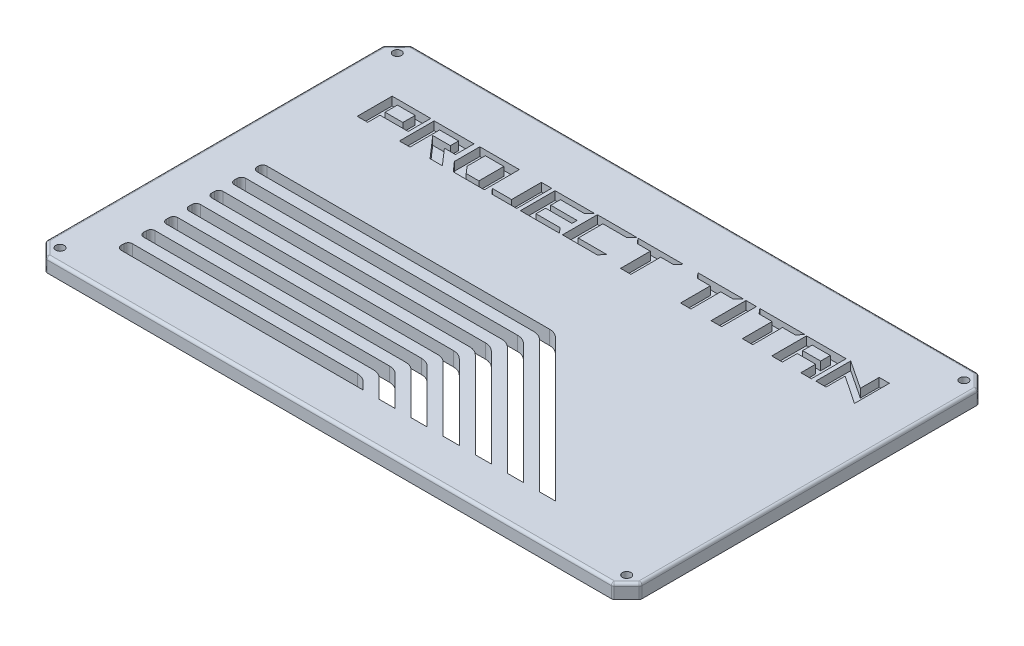
SolidWorks part; units mm, degrees
ref_plane "Front Plane" through (0, 0, 0) normal (0, 0, 1) x (1, 0, 0)
ref_plane "Top Plane" through (0, 0, 0) normal (0, 1, 0) x (1, 0, 0)
ref_plane "Right Plane" through (0, 0, 0) normal (1, 0, 0) x (0, 0, -1)
sketch "Sketch1" plane through (0, 0, 0) normal (0, 1, 0) x (1, 0, 0)
  line L1 (52.5, -34.5) -> (-52.5, -34.5)
  line L2 (52.5, -34.5) -> (52.5, 34.5)
  line L3 (52.5, 34.5) -> (-52.5, 34.5)
  line L4 (-52.5, -34.5) -> (-52.5, 34.5)
  line L5 (52.5, -34.5) -> (-52.5, 34.5) construction
  line L6 (52.5, 34.5) -> (-52.5, -34.5) construction
  point P0 (0, 0)
  dimension "D1" = 105
  dimension "D2" = 69
extrude "Boss-Extrude1" add sketch "Sketch1" along normal blind 5
extrude "Cut-Extrude1" cut sketch "Sketch2" against normal through all
sketch "Sketch2" plane through (17.0721, 0, 5.1034) normal (0, -1, 0) x (-1, 0, 0)
  line L0 (59.7281, 33.0909) -> (-27.1079, 33.0909)
  line L1 (-27.1079, 33.0909) -> (-27.1079, -24.4081)
  line L2 (-27.1079, -24.4081) -> (59.7281, -24.4081)
  line L3 (59.7281, -24.4081) -> (59.7281, 33.0909)
  line L8 (-26.1079, -23.4081) -> (58.7281, -23.4081) construction
  line L9 (-26.1079, 32.0909) -> (-26.1079, -23.4081) construction
  line L10 (58.7281, 32.0909) -> (-26.1079, 32.0909) construction
  line L11 (58.7281, -23.4081) -> (58.7281, 32.0909) construction
extrude "Cut-Extrude2" cut sketch "Sketch3" against normal blind 1
sketch "Sketch3" plane through (17.0721, 0, 5.1034) normal (0, -1, 0) x (-1, 0, 0)
  line L1 (59.8221, 30.7659) -> (54.5248, 30.7659)
  line L2 (59.8221, 30.7659) -> (59.8221, -16.2341) construction
  line L3 (59.8221, -16.2341) -> (54.5248, -16.2341)
  line L8 (65.3221, 30.2659) -> (60.3221, 30.2659) construction
  line L9 (60.3221, 30.2659) -> (60.3221, -15.7341) construction
  line L10 (60.3221, -15.7341) -> (65.3221, -15.7341) construction
  line L11 (65.3221, -15.7341) -> (65.3221, 30.2659) construction
  line L12 (54.5248, 30.7659) -> (54.5248, -16.2341)
  line L20 (65.8221, 30.7659) -> (59.8221, 30.7659)
  line L21 (59.8221, 30.7659) -> (59.8221, -16.2341) construction
  line L22 (59.8221, -16.2341) -> (65.8221, -16.2341)
  line L23 (65.8221, -16.2341) -> (65.8221, 30.7659)
extrude "Cut-Extrude3" cut sketch "Sketch4" against normal blind 1 contours L31 L28 L29 L17 L16 L19 | L19 L16 L17 | L30 L31 L19 L18 L17 L29 | L18 L19 L17 region at (15.76, 0, -28.9025) region at (12.8295, 0, -28.9025)
sketch "Sketch4" plane through (17.0721, 0, 5.1034) normal (0, -1, 0) x (-1, 0, 0)
  line L8 (69.5721, -29.3966) -> (69.5721, 69.6034)
  line L10 (-35.4279, 69.6034) -> (-35.4279, -29.3966)
  line L11 (-35.4279, -29.3966) -> (69.5721, -29.3966)
  line L16 (3.8121, 35.2559) -> (-1.1879, 35.2559)
  line L17 (-1.1879, 35.2559) -> (-1.1879, 32.7559)
  line L18 (-1.1879, 32.7559) -> (3.8121, 32.7559)
  line L19 (3.8121, 32.7559) -> (3.8121, 35.2559)
  line L20 (69.5721, 69.6034) -> (-35.4279, 69.6034)
  line L28 (4.3121, 35.7559) -> (-1.6879, 35.7559)
  line L29 (-1.6879, 35.7559) -> (-1.6879, 32.2559)
  line L30 (-1.6879, 32.2559) -> (4.3121, 32.2559)
  line L31 (4.3121, 32.2559) -> (4.3121, 35.7559)
extrude "Cut-Extrude4" cut sketch "Sketch5" against normal through all contours L3 L2 A3 L5 A2 L4 | L2 L3 L4 A4 L6 A5 region at (42.0883, 0, 0.4104)
sketch "Sketch5" plane through (17.0721, 0, 5.1034) normal (0, -1, 0) x (-1, 0, 0)
  line L2 (-27.1779, 33.1034) -> (-27.1779, 13.8376)
  line L3 (-27.1779, 5.1034) -> (-31.6779, 5.1034) construction
  line L4 (-31.6779, -0.8966) -> (-31.6779, 11.1034)
  line L5 (-30.1159, 12.6653) -> (-28.3501, 12.6653)
  line L6 (-29.4785, -3.0961) -> (-28.6478, -3.0961)
  line L7 (-27.1779, 5.1034) -> (-27.1779, 13.8376) construction
  line L8 (-27.1779, -4.566) -> (-18.8659, -4.566)
  line L9 (-27.1779, -4.566) -> (-27.1779, 5.1034)
  line L10 (-27.1779, 13.8376) -> (-18.8659, 13.8376)
  line L11 (-18.8659, -4.566) -> (-18.8659, 13.8376)
  line L12 (-27.1779, 13.8376) -> (-27.1779, 5.1034) construction
  line L13 (-27.1779, 5.1034) -> (-27.1779, -22.8966)
  arc A2 (-31.6779, 11.1034) -> (-30.1159, 12.6653) centre (-30.1159, 11.1034) cw
  arc A3 (-28.3501, 12.6653) -> (-27.1779, 13.8376) centre (-28.3501, 13.8376) ccw
  arc A4 (-31.6779, -0.8966) -> (-29.4785, -3.0961) centre (-29.4785, -0.8966) ccw
  arc A5 (-28.6478, -3.0961) -> (-27.1779, -4.566) centre (-28.6478, -4.566) cw
  point P8 (-31.6779, 5.1034)
extrude "Cut-Extrude7" cut sketch "Sketch9" against normal blind 4
sketch "Sketch9" plane through (17.0721, 0, 5.1034) normal (0, -1, 0) x (-1, 0, 0)
  circle A4 centre (-28.6779, -22.8966) radius 1.5 construction
  circle A5 centre (62.8221, -22.8966) radius 1.5 construction
  circle A6 centre (62.8221, 33.1034) radius 1.5 construction
  circle A7 centre (-28.6779, 33.1034) radius 1.5 construction
  circle A8 centre (-28.6779, 33.1034) radius 1
  circle A9 centre (62.8221, 33.1034) radius 1
  circle A10 centre (-28.6779, -22.8966) radius 1
  circle A11 centre (62.8221, -22.8966) radius 1
sketch "Sketch7" plane through (0, 5, 0) normal (0, 1, 0) x (1, 0, 0)
  line L1 (52.5, 34.5) -> (-52.5, 34.5)
  line L2 (52.5, 34.5) -> (52.5, 64.5)
  line L3 (52.5, 64.5) -> (-52.5, 64.5)
  line L4 (-52.5, 34.5) -> (-52.5, 64.5)
  line L5 (-52.5, -34.5) -> (52.5, -34.5)
  line L6 (-52.5, -34.5) -> (-52.5, -64.5)
  line L7 (-52.5, -64.5) -> (52.5, -64.5)
  line L8 (52.5, -34.5) -> (52.5, -64.5)
  line M17 (-52.5, -34.5) -> (52.5, -34.5)
  dimension "D1" = 30
  dimension "D2" = 30
extrude "Boss-Extrude2" add sketch "Sketch7" against normal up to surface (5 mm away) contours L8 L5 L7 M17 | L1 L4 L3 L2 region at (0, 5, 49.5) up to face at (-45.75, 0, -29)
sketch "Sketch8" plane through (0, 5, 0) normal (0, 1, 0) x (1, 0, 0)
  line L0 (52.5, 29.2726) -> (52.5, 64.5) construction
  line L1 (52.5, -64.5) -> (52.5, 64.5) construction
  line L2 (52.5, 46.8863) -> (26.68, 46.8863) construction
  line L3 (-52.5, 64.5) -> (-52.5, -64.5) construction
  line L4 (19.635, 46.8863) -> (19.635, 53.4863) construction
  line L5 (37.68, 40.2863) -> (26.68, 40.2863)
  line L6 (37.68, 40.2863) -> (37.68, 53.4863)
  line L7 (37.68, 53.4863) -> (26.68, 53.4863)
  line L8 (26.68, 40.2863) -> (26.68, 53.4863)
  line L9 (37.68, 40.2863) -> (26.68, 53.4863) construction
  line L10 (37.68, 53.4863) -> (26.68, 40.2863) construction
  line L11 (19.635, 40.2863) -> (8.635, 40.2863) construction
  line L12 (8.635, 40.2863) -> (8.635, 46.8863) construction
  line L13 (19.635, 53.4863) -> (8.635, 53.4863) construction
  line L14 (1.59, 46.8863) -> (1.59, 53.4863) construction
  line L15 (1.59, 40.2863) -> (-9.41, 40.2863) construction
  line L16 (-9.41, 46.8863) -> (-9.41, 53.4863) construction
  line L17 (1.59, 53.4863) -> (-9.41, 53.4863) construction
  line L18 (-16.455, 40.2863) -> (-16.455, 46.8863) construction
  line L19 (-16.455, 40.2863) -> (-27.455, 40.2863) construction
  line L20 (-27.455, 40.2863) -> (-27.455, 46.8863) construction
  line L21 (-16.455, 53.4863) -> (-27.455, 53.4863) construction
  line L22 (-34.5, 40.2863) -> (-34.5, 46.8863) construction
  line L23 (-34.5, 40.2863) -> (-45.5, 40.2863) construction
  line L24 (-45.5, 40.2863) -> (-45.5, 46.8863) construction
  line L25 (-34.5, 53.4863) -> (-45.5, 53.4863) construction
  line L26 (-45.5, 46.8863) -> (-45.5, 53.4863) construction
  line L27 (-34.5, 46.8863) -> (-34.5, 53.4863) construction
  line L28 (-27.455, 46.8863) -> (-34.5, 46.8863) construction
  line L29 (-34.5, 46.8863) -> (-52.5, 46.8863) construction
  line L30 (-16.455, 46.8863) -> (-27.455, 46.8863) construction
  line L31 (-27.455, 46.8863) -> (-27.455, 53.4863) construction
  line L32 (-16.455, 46.8863) -> (-16.455, 53.4863) construction
  line L33 (1.59, 40.2863) -> (1.59, 46.8863) construction
  line L34 (-9.41, 40.2863) -> (-9.41, 46.8863) construction
  line L35 (-9.41, 46.8863) -> (-16.455, 46.8863) construction
  line L36 (8.635, 46.8863) -> (8.635, 53.4863) construction
  line L37 (8.635, 46.8863) -> (1.59, 46.8863) construction
  line L38 (1.59, 46.8863) -> (-9.41, 46.8863) construction
  line L39 (19.635, 40.2863) -> (19.635, 46.8863) construction
  line L40 (26.68, 46.8863) -> (19.635, 46.8863) construction
  line L41 (19.635, 46.8863) -> (8.635, 46.8863) construction
  point P9 (32.18, 46.8863)
  point P14 (-40, 53.4863)
  dimension "D1" = 13.2
  dimension "D2" = 11
  dimension "D3" = 20.32
  dimension "D5" = 12.5
  dimension "D6" = 11
  dimension "D4" = 5
extrude "Cut-Extrude6" cut sketch "Sketch8" against normal through all
sketch "Sketch10" plane through (0, 5, 0) normal (0, 1, 0) x (1, 0, 0)
  line L0 (44.18, 27.9875) -> (44.18, 8.7342) construction
  line L1 (-52.5, 64.5) -> (52.5, 64.5)
  line L2 (-52.5, 64.5) -> (-52.5, -34.5)
  line L3 (-52.5, -34.5) -> (52.5, -34.5) construction
  line L4 (52.5, 64.5) -> (52.5, -34.5)
  line L5 (44.18, -9.6693) -> (44.18, -29.5115) construction
  line L6 (44.18, -29.5115) -> (-42.656, -29.5115) construction
  line L7 (-42.656, -29.5115) -> (-42.656, 27.9875) construction
  line L8 (-42.656, 27.9875) -> (44.18, 27.9875) construction
  line L9 (37.68, 40.2863) -> (37.68, 53.4863) construction
  line L10 (26.68, 40.2863) -> (37.68, 40.2863) construction
  line L11 (37.68, 53.4863) -> (26.68, 53.4863) construction
  line L12 (26.68, 53.4863) -> (26.68, 40.2863) construction
  line L29 (44.18, 27.9875) -> (44.18, 8.7342)
  line L30 (44.18, -9.6693) -> (44.18, -29.5115)
  line L31 (44.18, -29.5115) -> (-42.656, -29.5115)
  line L32 (-42.656, -29.5115) -> (-42.656, 27.9875)
  line L33 (-42.656, 27.9875) -> (44.18, 27.9875)
  line L34 (37.68, 40.2863) -> (37.68, 53.4863)
  line L35 (26.68, 40.2863) -> (37.68, 40.2863)
  line L36 (37.68, 53.4863) -> (26.68, 53.4863)
  line L37 (26.68, 53.4863) -> (26.68, 40.2863)
  line L54 (44.18, -9.6693) -> (44.18, 8.7342)
  line L59 (-52.5, 64.5) -> (-52.5, -64.5)
  line L60 (-52.5, -64.5) -> (52.5, -64.5)
  line L61 (52.5, -64.5) -> (52.5, 64.5)
  line L62 (52.5, 64.5) -> (-52.5, 64.5)
  line L63 (-52.5, 64.5) -> (-52.5, -64.5)
  line L64 (-52.5, -64.5) -> (52.5, -64.5)
  line L65 (52.5, -64.5) -> (52.5, 64.5)
  line L66 (52.5, 64.5) -> (-52.5, 64.5)
  line M11 (26.68, 40.2863) -> (26.68, 53.4863)
  line M12 (26.68, 53.4863) -> (37.68, 53.4863)
  line M13 (37.68, 53.4863) -> (37.68, 40.2863)
  line M14 (37.68, 40.2863) -> (26.68, 40.2863)
  line M31 (44.18, 27.9875) -> (44.18, 8.7342)
  line M32 (44.18, 8.7342) -> (44.25, 8.7342)
  arc M33 (44.25, 8.7342) -> (45.4223, 7.562) centre (45.4223, 8.7342) ccw
  line M34 (45.4223, 7.562) -> (47.188, 7.562)
  arc M35 (47.188, 7.562) -> (48.75, 6) centre (47.188, 6) cw
  line M36 (48.75, 6) -> (48.75, -6)
  arc M37 (48.75, -6) -> (46.5506, -8.1994) centre (46.5506, -6) cw
  line M38 (46.5506, -8.1994) -> (45.7199, -8.1994)
  arc M39 (45.7199, -8.1994) -> (44.25, -9.6693) centre (45.7199, -9.6693) ccw
  line M40 (44.25, -9.6693) -> (44.18, -9.6693)
  line M41 (44.18, -9.6693) -> (44.18, -29.5115)
  line M42 (44.18, -29.5115) -> (-42.656, -29.5115)
  line M43 (-42.656, -29.5115) -> (-42.656, 27.9875)
  line M44 (-42.656, 27.9875) -> (44.18, 27.9875)
  line M45 (-52.5, 64.5) -> (-52.5, -64.5)
  line M47 (52.5, -64.5) -> (52.5, 64.5)
  line M48 (52.5, 64.5) -> (-52.5, 64.5)
  line M70 (-52.5, -64.5) -> (52.5, -64.5)
  dimension "D1" = 0
extrude "Boss-Extrude3" add sketch "Sketch10" along normal blind 2 contours L3 M45 M47 M48 M44 M31 M32 M33 M34 M35 M36 M37 M38 M39 M40 M41 M42 M43 M14 M11 M12 M13 | L3 M45 M70 M47 | L54 M40 M39 M38 M37 M36 M35 M34 M33 M32 region at (-2.2738, 5, -29.4948) region at (0, 5, 49.5) region at (46.3986, 5, 0.2889)
sketch "Sketch11" plane through (0, 7, 0) normal (0, 1, 0) x (1, 0, 0)
  line L4 (-42.656, 27.9875) -> (-42.656, -29.5115)
  line L5 (44.18, 27.9875) -> (-42.656, 27.9875)
  line L6 (-42.656, -29.5115) -> (44.18, -29.5115)
  line L7 (44.18, -29.5115) -> (44.18, 27.9875)
  line L8 (36.68, -29.5115) -> (36.68, -27.5115) construction
  line L9 (44.18, -29.5115) -> (36.68, -29.5115)
  line L10 (44.18, -29.5115) -> (44.18, 27.9875)
  line L11 (44.18, 27.9875) -> (36.68, 27.9875)
  line L12 (36.68, -27.5115) -> (36.68, 25.9875)
  line L13 (-42.656, -29.5115) -> (36.68, -29.5115)
  line L14 (-42.656, -29.5115) -> (-42.656, -27.5115)
  line L15 (-40.656, -27.5115) -> (36.68, -27.5115)
  line L16 (36.68, -29.5115) -> (36.68, -27.5115) construction
  line L17 (-42.656, 27.9875) -> (36.68, 27.9875)
  line L18 (-42.656, 27.9875) -> (-42.656, 25.9875)
  line L19 (-40.656, 25.9875) -> (36.68, 25.9875)
  line L20 (36.68, 27.9875) -> (36.68, 25.9875) construction
  line L21 (-42.656, 27.9875) -> (-40.656, 27.9875)
  line L22 (-42.656, 27.9875) -> (-42.656, -29.5115)
  line L23 (-42.656, -29.5115) -> (-40.656, -29.5115)
  line L24 (-40.656, 25.9875) -> (-40.656, -27.5115)
  line L25 (-40.656, -27.5115) -> (-40.656, -29.5115) construction
  line L26 (-42.656, -27.5115) -> (-40.656, -27.5115) construction
  line L27 (-42.656, 25.9875) -> (-40.656, 25.9875) construction
  line L28 (-40.656, 27.9875) -> (-40.656, 25.9875) construction
  line L29 (36.68, 25.9875) -> (36.68, 27.9875) construction
  dimension "D1" = 7.5
  dimension "D2" = 2
  dimension "D3" = 2
  dimension "D4" = 2
extrude "Boss-Extrude4" add sketch "Sketch11" against normal blind 2 contours L13 L6 L5 L17 L4 L24 L19 L12 L15 region at (-41.656, 7, -26.946)
chamfer "Chamfer1" distance 1 angle 45 4 edges at (-1.988, 7, -25.9875) (-40.656, 7, 0.762) (-1.988, 7, 27.5115) (36.68, 7, 0.762)
sketch "Sketch12" plane through (0, 7, 0) normal (0, 1, 0) x (1, 0, 0)
  line L0 (-52.5, -64.5) -> (52.5, -64.5) construction
  line L1 (-52.5, -64.5) -> (-117.5, -64.5)
  line L2 (-52.5, -64.5) -> (-52.5, 64.5)
  line L3 (-52.5, 64.5) -> (-117.5, 64.5)
  line L4 (-117.5, -64.5) -> (-117.5, 64.5)
  line L5 (52.5, -64.5) -> (117.5, -64.5)
  line L6 (52.5, -64.5) -> (52.5, 64.5)
  line L7 (52.5, 64.5) -> (117.5, 64.5)
  line L8 (117.5, -64.5) -> (117.5, 64.5)
  line L9 (52.5, 64.5) -> (-52.5, 64.5) construction
  line L10 (-67.5, -28) -> (-102.5, -28) construction
  line L11 (-85, -45.5) -> (-85, -10.5) construction
  circle A0 centre (-85, -10.5) radius 6
  circle A1 centre (-85, -45.5) radius 6
  circle A2 centre (-102.5, -28) radius 6
  circle A3 centre (-67.5, -28) radius 6
  circle A4 centre (-85, -10.5) radius 8.5 construction
  circle A5 centre (-102.5, -28) radius 8.5 construction
  circle A6 centre (-67.5, -28) radius 8.5 construction
  circle A7 centre (-85, -45.5) radius 8.5 construction
  point P4 (-85, 64.5)
  point P19 (-85, -28)
  line M72 (-52.5, 64.5) -> (-52.5, -64.5)
  dimension "D3" = 12
  dimension "D7" = 17
  dimension "D8" = 17
  dimension "D1" = 65
  dimension "D2" = 65
  dimension "D4" = 35
  dimension "D5" = 75
  dimension "D6" = 35
extrude "Boss-Extrude5" add sketch "Sketch12" against normal up to surface (7 mm away) contours L4 L1 L3 M72 region at (-85, 7, -1.5968) up to face at (32.18, 0, -46.8863)
sketch "Sketch15" plane through (0, 7, 0) normal (0, 1, 0) x (1, 0, 0)
  line L0 (-117.5, -64.5) -> (52.5, -64.5) construction
  line L1 (-41.656, -28.5115) -> (37.68, -28.5115)
  line L2 (-41.656, -28.5115) -> (-41.656, -64.5)
  line L3 (-41.656, -64.5) -> (37.68, -64.5)
  line L4 (37.68, -28.5115) -> (37.68, -64.5)
  line L5 (-41.656, -46.5057) -> (37.68, -46.5057) construction
  circle A0 centre (-32.041, -46.5057) radius 3.1
  circle A1 centre (-12.041, -46.5057) radius 3.1
  circle A2 centre (7.959, -46.5057) radius 3.1
  circle A3 centre (27.959, -46.5057) radius 3.1
  dimension "D1" = 6.2
  dimension "D2" = 9.615
  dimension "D3" = 4
extrude "Cut-Extrude8" cut sketch "Sketch15" against normal through all contours A0 L5 | A1 L5 | L5 A1 | L5 A0 | A2 L5 | L5 A2 | A3 L5 | L5 A3 | A1 region at (-32.041, 7, 45.1901) region at (-32.041, 7, 47.8214) region at (27.959, 7, 47.8214) region at (27.959, 7, 45.1901) region at (-12.041, 7, 45.1901) region at (-12.041, 7, 47.8214) region at (7.959, 7, 47.8214) region at (7.959, 7, 45.1901)
sketch "Sketch16" plane through (0, 0, 0) normal (0, -1, 0) x (1, 0, 0)
  circle A0 centre (27.959, 46.5057) radius 3.1 construction
  circle A1 centre (7.959, 46.5057) radius 3.1 construction
  circle A2 centre (-12.041, 46.5057) radius 3.1 construction
  circle A3 centre (-32.041, 46.5057) radius 3.1 construction
  circle A4 centre (27.959, 46.5057) radius 3.1
  circle A5 centre (7.959, 46.5057) radius 3.1
  circle A6 centre (-12.041, 46.5057) radius 3.1
  circle A7 centre (-32.041, 46.5057) radius 3.1
  circle A8 centre (-32.041, 46.5057) radius 5.5
  circle A9 centre (-12.041, 46.5057) radius 5.5
  circle A10 centre (7.959, 46.5057) radius 5.5
  circle A11 centre (27.959, 46.5057) radius 5.5
  dimension "D1" = 11
extrude "Cut-Extrude9" cut sketch "Sketch16" against normal blind 3
sketch "Sketch18" plane through (0, 0, 0) normal (0, -1, 0) x (1, 0, 0)
  circle A0 centre (-85, 45.5) radius 10
  circle A1 centre (-102.5, 28) radius 10
  circle A2 centre (-85, 10.5) radius 10
  circle A3 centre (-67.5, 28) radius 10
  dimension "D1" = 20
extrude "Cut-Extrude10" cut sketch "Sketch18" against normal blind 3
chamfer "Chamfer2" distance 1 angle 45 4 edges at (-85, 0, 0.5) (-67.5, 0, 18) (-102.5, 0, 18) (-85, 0, 35.5)
sketch "Sketch19" plane through (0, 0, 0) normal (0, -1, 0) x (1, 0, 0)
  line L0 (-117.5, -64.5) -> (52.5, -64.5) construction
  line L1 (-42.656, -27.9875) -> (26.68, -27.9875)
  line L2 (-42.656, -27.9875) -> (-42.656, -64.5)
  line L4 (26.68, -27.9875) -> (26.68, -64.5)
  line L5 (26.68, -64.5) -> (-7.988, -64.5) construction
  line L6 (26.68, -64.5) -> (-7.988, -64.5) construction
  line L7 (18.196, -64.5) -> (0.496, -64.5)
  line L8 (18.196, -64.5) -> (18.196, -51)
  line L9 (18.196, -51) -> (0.496, -51)
  line L10 (0.496, -64.5) -> (0.496, -51)
  point P12 (9.346, -64.5)
  point P13 (9.346, -64.5)
  line M50 (-117.5, -64.5) -> (52.5, -64.5)
  dimension "D1" = 17.7
  dimension "D2" = 13.5
extrude "Cut-Extrude11" cut sketch "Sketch19" against normal blind 2 contours L10 L8 L9 M50 region at (9.346, 0, -57.75)
sketch "Sketch20" plane through (0, 2, 0) normal (0, -1, 0) x (1, 0, 0)
  line L0 (5.496, -62.5) -> (10.696, -62.5) construction
  line L1 (5.496, -61.0866) -> (10.696, -61.0866)
  line L3 (18.196, -64.5) -> (18.196, -51) construction
  line L4 (0.496, -64.5) -> (0.496, -51) construction
  line L5 (0.496, -64.5) -> (18.196, -64.5) construction
  line L6 (18.196, -64.5) -> (18.196, -51) construction
  line L7 (0.496, -64.5) -> (18.196, -64.5)
  line L8 (0.496, -64.5) -> (0.496, -61.0866)
  line L9 (0.496, -61.0866) -> (18.196, -61.0866)
  line L10 (18.196, -64.5) -> (18.196, -61.0866)
  line L12 (0.496, -51) -> (18.196, -51)
  line L13 (0.496, -51) -> (0.496, -55.2225)
  line L14 (0.496, -55.2225) -> (18.196, -55.2225)
  line L15 (18.196, -51) -> (18.196, -55.2225)
  point P2 (8.096, -62.5)
  line M2 (0.496, -51) -> (0.496, -64.5)
  line M4 (18.196, -64.5) -> (18.196, -51)
  line M5 (18.196, -51) -> (0.496, -51)
  dimension "D1" = 7.5
  dimension "D2" = 5
  dimension "D3" = 2
extrude "Cut-Extrude12" cut sketch "Sketch20" against normal blind 1 contours L10 L9 L1 | L14 M2 M4 M5 region at (9.346, 2, -62.7933) region at (9.346, 2, -53.1112)
sketch "Sketch22" plane through (0, 0, 0) normal (0, -1, 0) x (1, 0, 0)
  line L0 (-117.5, -64.5) -> (0.496, -64.5) construction
  line L1 (-24.8391, -64.5) -> (-60.3391, -64.5)
  line L2 (-24.8391, -64.5) -> (-24.8391, -54.5)
  line L3 (-24.8391, -54.5) -> (-60.3391, -54.5)
  line L4 (-60.3391, -64.5) -> (-60.3391, -54.5)
  circle A0 centre (-57.8391, -59.5) radius 1
  dimension "D4" = 2
  dimension "D1" = 10
  dimension "D2" = 35.5
  dimension "D3" = 2.5
extrude "Cut-Extrude13" cut sketch "Sketch22" against normal blind 2
sketch "Sketch23" plane through (0, 0, 0) normal (0, -1, 0) x (1, 0, 0)
  circle A1 centre (-57.8391, -59.5) radius 1
  circle A2 centre (-57.8391, -59.5) radius 1
  dimension "D1" = 0
extrude "Cut-Extrude14" cut sketch "Sketch23" against normal blind 4
sketch "Sketch24" plane through (0, 2, 0) normal (0, -1, 0) x (1, 0, 0)
  line L0 (-35.8391, -63) -> (-25.8391, -63) construction
  line L1 (-35.8391, -62.0036) -> (-25.8391, -62.0036)
  line L2 (-35.8391, -63.9964) -> (-25.8391, -63.9964)
  line L3 (-60.3391, -64.5) -> (-24.8391, -64.5) construction
  line L4 (-24.8391, -64.5) -> (-24.8391, -54.5) construction
  arc A0 (-35.8391, -62.0036) -> (-35.8391, -63.9964) centre (-35.8391, -63) ccw
  arc A1 (-25.8391, -63.9964) -> (-25.8391, -62.0036) centre (-25.8391, -63) ccw
  point P2 (-30.8391, -63)
  dimension "D1" = 1.5
  dimension "D2" = 6
  dimension "D3" = 10
extrude "Cut-Extrude15" cut sketch "Sketch24" against normal blind 1
sketch "Sketch25" plane through (0, 7, 0) normal (0, 1, 0) x (1, 0, 0)
  line L0 (52.5, 64.5) -> (-117.5, 64.5) construction
  line L1 (-117.5, -64.5) -> (-117.5, 64.5) construction
  circle A0 centre (-102.5, 44.5) radius 3.1
  circle A1 centre (-82.5, 44.5) radius 3.1
  dimension "D1" = 6.2
  dimension "D2" = 20
  dimension "D3" = 20
  dimension "D4" = 15
extrude "Cut-Extrude16" cut sketch "Sketch25" against normal through all
sketch "Sketch26" plane through (0, 0, 0) normal (0, -1, 0) x (1, 0, 0)
  circle A0 centre (-102.5, -44.5) radius 5.15
  circle A1 centre (-82.5, -44.5) radius 5.15
  dimension "D1" = 10.3
extrude "Cut-Extrude17" cut sketch "Sketch26" against normal blind 4
sketch "Sketch27" plane through (0, 7, 0) normal (0, 1, 0) x (1, 0, 0)
  line L1 (52.5, 64.5) -> (92.5, 64.5)
  line L2 (52.5, 64.5) -> (52.5, -64.5)
  line L3 (52.5, -64.5) -> (92.5, -64.5)
  line L4 (92.5, 64.5) -> (92.5, -64.5)
  dimension "D1" = 40
extrude "Boss-Extrude6" add sketch "Sketch27" against normal up to surface (7 mm away) up to face at (-102.5, 0, -49.65)
pattern_linear "LPattern1" count 2 spacing 40 along (1, 0, 0) of "Cut-Extrude17", "Cut-Extrude16"
sketch "Sketch28" plane through (0, 7, 0) normal (0, 1, 0) x (1, 0, 0)
  line L0 (37.68, -0.762) -> (92.5, 0) construction
  line L1 (37.68, 26.9875) -> (37.68, -28.5115) construction
  line L2 (92.5, -64.5) -> (92.5, 64.5) construction
  line L3 (37.68, -0.762) -> (65.09, -0.381)
  line L4 (92.5, 64.5) -> (-117.5, 64.5) construction
  line L6 (65.09, -0.381) -> (65.09, -64.5) construction
  line L7 (-117.5, -64.5) -> (92.5, -64.5) construction
  line L8 (72.5, 32.0595) -> (72.5, 64.5) construction
  circle A0 centre (62.5, 48.2798) radius 3.45
  circle A1 centre (62.5, 48.2798) radius 11.75 construction
  circle A2 centre (62.5, 16.2798) radius 3.45
  circle A3 centre (62.5, 16.2798) radius 11.75 construction
  circle A4 centre (62.5, -15.7202) radius 3.45
  circle A5 centre (62.5, -15.7202) radius 11.75 construction
  circle A6 centre (62.5, -47.7202) radius 3.45
  circle A7 centre (62.5, -47.7202) radius 11.75 construction
  point P17 (72.5, 48.2798)
  dimension "D2" = 6.9
  dimension "D3" = 30
  dimension "D1" = 4
extrude "Cut-Extrude18" cut sketch "Sketch28" against normal through all contours A0 | A2 | A4 | A6 region at (62.5, 7, -48.2798) region at (62.5, 7, -16.2798) region at (62.5, 7, 15.7202) region at (62.5, 7, 47.7202)
sketch "Sketch29" plane through (0, 7, 0) normal (0, 1, 0) x (1, 0, 0)
  line L0 (74.25, 48.2798) -> (92.5, 48.2798) construction
  line L1 (92.5, -64.5) -> (92.5, 64.5) construction
  circle A0 centre (62.5, 48.2798) radius 11.75 construction
  circle A1 centre (83.375, 48.2798) radius 3.45
  circle A2 centre (83.375, 16.2798) radius 3.45
  circle A3 centre (83.375, -15.7202) radius 3.45
  circle A4 centre (83.375, -47.7202) radius 3.45
  dimension "D1" = 6.9
  dimension "D2" = 4
extrude "Cut-Extrude19" cut sketch "Sketch29" against normal through all
sketch "Sketch30" plane through (0, 0, 0) normal (0, -1, 0) x (1, 0, 0)
  circle A0 centre (83.375, -48.2798) radius 5
  circle A1 centre (83.375, -16.2798) radius 5
  circle A2 centre (83.375, 15.7202) radius 5
  circle A3 centre (83.375, 47.7202) radius 5
  dimension "D1" = 10
  dimension "D2" = 4
extrude "Cut-Extrude20" cut sketch "Sketch30" against normal blind 4.5
sketch "Sketch31" plane through (0, 0, 0) normal (0, -1, 0) x (1, 0, 0)
  circle A0 centre (62.5, 47.7202) radius 5.5
  circle A1 centre (62.5, 15.7202) radius 5.5
  circle A2 centre (62.5, -16.2798) radius 5.5
  circle A3 centre (62.5, -48.2798) radius 5.5
  dimension "D1" = 11
  dimension "D2" = 4
extrude "Cut-Extrude21" cut sketch "Sketch31" against normal blind 2
sketch "Sketch32" plane through (0, 0, 0) normal (0, -1, 0) x (1, 0, 0)
  line L0 (69.9505, 49.2202) -> (70.9682, 49.2202)
  line L2 (61, 56.1884) -> (61, 55.1708)
  line L4 (64, 56.1884) -> (64, 55.1708)
  line L5 (54.0318, 49.2202) -> (55.0495, 49.2202)
  line L7 (54.0318, 46.2202) -> (55.0495, 46.2202)
  line L9 (69.9505, 46.2202) -> (70.9682, 46.2202)
  line L12 (64, 40.2697) -> (64, 39.2521)
  line L13 (61, 40.2697) -> (61, 39.2521)
  arc A0 (54.0318, 49.2202) -> (54.0318, 46.2202) centre (62.5, 47.7202) ccw
  arc A1 (55.0495, 49.2202) -> (55.0495, 46.2202) centre (62.5, 47.7202) ccw
  circle A2 centre (62.5, 47.7202) radius 8.6 construction
  circle A3 centre (62.5, 47.7202) radius 7.6 construction
  arc A4 (64, 56.1884) -> (61, 56.1884) centre (62.5, 47.7202) ccw
  arc A5 (64, 55.1708) -> (61, 55.1708) centre (62.5, 47.7202) ccw
  arc A6 (70.9682, 46.2202) -> (70.9682, 49.2202) centre (62.5, 47.7202) ccw
  arc A7 (69.9505, 46.2202) -> (69.9505, 49.2202) centre (62.5, 47.7202) ccw
  arc A8 (61, 39.2521) -> (64, 39.2521) centre (62.5, 47.7202) ccw
  arc A9 (61, 40.2697) -> (64, 40.2697) centre (62.5, 47.7202) ccw
  dimension "D1" = 1
  dimension "17.2" = 17.2
  dimension "D3" = 3
extrude "Cut-Extrude22" cut sketch "Sketch32" against normal blind 2.5
pattern_linear "LPattern2" count 4 spacing 32 along (0, 0, -1) of "Cut-Extrude22"
sketch "Sketch33" plane through (0, 7, 0) normal (0, 1, 0) x (1, 0, 0)
  circle A0 centre (-52.041, -46.5057) radius 6
  circle A1 centre (-67.5, -28) radius 6 construction
  circle A2 centre (-32.041, -46.5057) radius 3.1 construction
  circle A3 centre (-67.5, -28) radius 6
  circle A4 centre (-32.041, -46.5057) radius 3.1
  dimension "D1" = 20
extrude "Cut-Extrude23" cut sketch "Sketch33" against normal through all contours A0 region at (-52.041, 7, 46.5057)
sketch "Sketch34" plane through (0, 0, 0) normal (0, -1, 0) x (1, 0, 0)
  circle A0 centre (-52.041, 46.5057) radius 10
  circle A1 centre (-67.5, 28) radius 10 construction
  circle A2 centre (-67.5, 28) radius 10
extrude "Cut-Extrude24" cut sketch "Sketch34" against normal up to surface (3 mm away) contours A0 region at (-52.041, 0, 46.5057) up to face at (-67.5, 3, 18)
chamfer "Chamfer3" distance 1 angle 45 1 edges at (-52.041, 0, 36.5057)
chamfer "Chamfer4" distance 5 angle 45 4 edges at (92.5, 3.5, -64.5) (92.5, 3.5, 64.5) (-117.5, 3.5, 64.5) (-117.5, 3.5, -64.5)
fillet "Fillet1" radius 1 16 edges at (87.5, 3.5, 64.5) (92.5, 3.5, 59.5) (-112.5, 3.5, 64.5) (-117.5, 3.5, 59.5) (-117.5, 3.5, -59.5) (-112.5, 3.5, -64.5) (90, 7, 62) (-12.5, 7, 64.5) (-115, 7, 62) (-117.5, 7, 0) (-115, 7, -62) (-12.5, 7, -64.5) (87.5, 3.5, -64.5) (92.5, 3.5, -59.5) (92.5, 7, 0) (90, 7, -62)
sketch "Sketch36" plane through (0, 0, 0) normal (0, -1, 0) x (1, 0, 0)
  line L8 (-115, 62) -> (-110.0537, 57.0537) construction
  line L9 (-112.7929, 64.2071) -> (-117.2071, 59.7929) construction
  line L10 (-115, -62) -> (-110.0503, -57.0503) construction
  line L11 (-117.2071, -59.7929) -> (-112.7929, -64.2071) construction
  line L12 (90, -62) -> (85.0503, -57.0503) construction
  line L13 (87.7929, -64.2071) -> (92.2071, -59.7929) construction
  line L14 (90, 62) -> (85.0503, 57.0503) construction
  line L15 (92.2071, 59.7929) -> (87.7929, 64.2071) construction
  circle A0 centre (-112.5268, 59.5268) radius 1.5
  circle A1 centre (-112.5251, -59.5251) radius 1.5
  circle A2 centre (87.5251, -59.5251) radius 1.5
  circle A3 centre (87.5251, 59.5251) radius 1.5
  dimension "D1" = 3
  dimension "D4" = 3
  dimension "D6" = 3
  dimension "D8" = 3
  dimension "D2" = 6.9952
  dimension "D3" = 7
  dimension "D5" = 7
  dimension "D7" = 7
extrude "Cut-Extrude25" cut sketch "Sketch36" against normal through all contours A3 | A2 | A1 | A0 | A3 region at (-112.5268, 0, 59.5268) region at (-112.5251, 0, -59.5251) region at (87.5251, 0, -59.5251) region at (87.5251, 0, 59.5251)
sketch "Sketch38" plane through (0, 0, 0) normal (0, -1, 0) x (1, 0, 0)
  line L0 (-117.5, -24.3675) -> (-48.75, -24.3675) construction
  line L2 (-48.75, 21.3375) -> (-48.75, -25.6625) construction
  line L3 (-117.5, -59.0858) -> (-117.5, 59.0858) construction
  text T0 "PROJECT TITAN\r\nJUST BETTER\r\n2025" font "ROG Fonts" height in points 16
extrude "Cut-Extrude27" cut sketch "Sketch38" against normal blind 2
sketch "Sketch39" plane through (0, 7, 0) normal (0, 1, 0) x (1, 0, 0)
  line L8 (-112.0858, -63.5) -> (87.0858, -63.5)
  line L9 (87.0858, -63.5) -> (91.5, -59.0858)
  line L10 (91.5, -59.0858) -> (91.5, 59.0858)
  line L11 (91.5, 59.0858) -> (87.0858, 63.5)
  line L12 (87.0858, 63.5) -> (-112.0858, 63.5)
  line L13 (-112.0858, 63.5) -> (-116.5, 59.0858)
  line L14 (-116.5, 59.0858) -> (-116.5, -59.0858)
  line L15 (-116.5, -59.0858) -> (-112.0858, -63.5)
  line L16 (-112.0858, -63.5) -> (87.0858, -63.5)
  line L17 (87.0858, -63.5) -> (91.5, -59.0858)
  line L18 (91.5, -59.0858) -> (91.5, 59.0858)
  line L19 (91.5, 59.0858) -> (87.0858, 63.5)
  line L20 (87.0858, 63.5) -> (-112.0858, 63.5)
  line L21 (-112.0858, 63.5) -> (-116.5, 59.0858)
  line L22 (-116.5, 59.0858) -> (-116.5, -59.0858)
  line L23 (-116.5, -59.0858) -> (-112.0858, -63.5)
  dimension "D1" = 0
sketch "Sketch40" plane through (0, 7, 0) normal (0, 1, 0) x (1, 0, 0)
  line L0 (-24.8391, 64.5) -> (-24.8391, 54.5) construction
  line L1 (0.496, 64.5) -> (0.496, 51) construction
  line L2 (-24.8391, 64.5) -> (-24.8391, 54.5)
  line L3 (0.496, 64.5) -> (0.496, 51)
  line L4 (-24.8391, 59.5) -> (0.496, 59.5) construction
  line L5 (0.496, 59.5) -> (-12.1715, 59.5) construction
  line L6 (-12.1715, 59.5) -> (-12.1715, 64.5) construction
  line L7 (-112.0858, 64.5) -> (87.0858, 64.5) construction
  line L8 (-12.1715, 64.5) -> (-12.1715, 25.9875) construction
  line L9 (36.68, 25.9875) -> (-40.656, 25.9875) construction
  line L11 (-4.1715, 30.2437) -> (-20.1715, 30.2437)
  line L12 (-4.1715, 30.2437) -> (-4.1715, 60.2437)
  line L13 (-4.1715, 60.2437) -> (-20.1715, 60.2437)
  line L14 (-20.1715, 30.2437) -> (-20.1715, 60.2437)
  line L15 (-4.1715, 30.2437) -> (-20.1715, 60.2437) construction
  line L16 (-4.1715, 60.2437) -> (-20.1715, 30.2437) construction
  circle A0 centre (-12.1715, 45.2437) radius 6
  dimension "D1" = 30
  dimension "D2" = 16
extrude "Cut-Extrude28" cut sketch "Sketch40" against normal through all contours A0 region at (-12.1715, 7, -45.2437)
sketch "Sketch41" plane through (0, 0, 0) normal (0, -1, 0) x (1, 0, 0)
  line L1 (-60.3391, -64.5) -> (18.196, -64.5)
  line L16 (92.2071, 59.7929) -> (87.7929, 64.2071)
  line L17 (87.0858, 64.5) -> (-112.0858, 64.5)
  line L18 (-112.7929, 64.2071) -> (-117.2071, 59.7929)
  line L19 (-117.5, 59.0858) -> (-117.5, -59.0858)
  line L20 (-117.2071, -59.7929) -> (-112.7929, -64.2071)
  line L21 (-112.0858, -64.5) -> (-60.3391, -64.5)
  line L22 (-60.3391, -64.5) -> (-60.3391, -54.5)
  line L23 (-60.3391, -54.5) -> (-24.8391, -54.5)
  line L24 (-24.8391, -54.5) -> (-24.8391, -64.5)
  line L25 (-24.8391, -64.5) -> (0.496, -64.5)
  line L26 (0.496, -64.5) -> (0.496, -51)
  line L27 (0.496, -51) -> (18.196, -51)
  line L28 (18.196, -51) -> (18.196, -64.5)
  line L29 (18.196, -64.5) -> (87.0858, -64.5)
  line L30 (87.7929, -64.2071) -> (92.2071, -59.7929)
  line L31 (92.5, -59.0858) -> (92.5, 59.0858)
  line L32 (92.2071, 59.7929) -> (87.7929, 64.2071)
  line L33 (87.0858, 64.5) -> (-112.0858, 64.5)
  line L34 (-112.7929, 64.2071) -> (-117.2071, 59.7929)
  line L35 (-117.5, 59.0858) -> (-117.5, -59.0858)
  line L36 (-117.2071, -59.7929) -> (-112.7929, -64.2071)
  line L37 (-112.0858, -64.5) -> (-60.3391, -64.5)
  line L45 (18.196, -64.5) -> (87.0858, -64.5)
  line L46 (87.7929, -64.2071) -> (92.2071, -59.7929)
  line L47 (92.5, -59.0858) -> (92.5, 59.0858)
  circle A0 centre (-112.5251, -59.5251) radius 1.5 construction
  circle A1 centre (87.5251, -59.5251) radius 1.5 construction
  circle A2 centre (87.5251, 59.5251) radius 1.5 construction
  circle A3 centre (-112.5268, 59.5268) radius 1.5 construction
  circle A4 centre (-112.5251, -59.5251) radius 1.5
  circle A5 centre (87.5251, -59.5251) radius 1.5
  circle A6 centre (87.5251, 59.5251) radius 1.5
  circle A7 centre (-112.5268, 59.5268) radius 1.5
  arc A8 (87.7929, 64.2071) -> (87.0858, 64.5) centre (87.0858, 63.5) ccw
  arc A9 (-112.0858, 64.5) -> (-112.7929, 64.2071) centre (-112.0858, 63.5) ccw
  arc A10 (-117.2071, 59.7929) -> (-117.5, 59.0858) centre (-116.5, 59.0858) ccw
  arc A11 (-117.5, -59.0858) -> (-117.2071, -59.7929) centre (-116.5, -59.0858) ccw
  arc A12 (-112.7929, -64.2071) -> (-112.0858, -64.5) centre (-112.0858, -63.5) ccw
  arc A13 (87.0858, -64.5) -> (87.7929, -64.2071) centre (87.0858, -63.5) ccw
  arc A14 (92.2071, -59.7929) -> (92.5, -59.0858) centre (91.5, -59.0858) ccw
  arc A15 (92.5, 59.0858) -> (92.2071, 59.7929) centre (91.5, 59.0858) ccw
  arc A16 (87.7929, 64.2071) -> (87.0858, 64.5) centre (87.0858, 63.5) ccw
  arc A17 (-112.0858, 64.5) -> (-112.7929, 64.2071) centre (-112.0858, 63.5) ccw
  arc A18 (-117.2071, 59.7929) -> (-117.5, 59.0858) centre (-116.5, 59.0858) ccw
  arc A19 (-117.5, -59.0858) -> (-117.2071, -59.7929) centre (-116.5, -59.0858) ccw
  arc A20 (-112.7929, -64.2071) -> (-112.0858, -64.5) centre (-112.0858, -63.5) ccw
  arc A21 (87.0858, -64.5) -> (87.7929, -64.2071) centre (87.0858, -63.5) ccw
  arc A22 (92.2071, -59.7929) -> (92.5, -59.0858) centre (91.5, -59.0858) ccw
  arc A23 (92.5, 59.0858) -> (92.2071, 59.7929) centre (91.5, 59.0858) ccw
  dimension "D1" = 0
extrude "Boss-Extrude7" add sketch "Sketch41" against normal up to surface (7 mm away) up to face at (-12.1715, 7, -39.2437)
sketch "Sketch42" plane through (0, 7, 0) normal (0, 1, 0) x (1, 0, 0)
  line L8 (92.5, -59.0858) -> (92.5, 59.0858)
  line L9 (92.2071, 59.7929) -> (87.7929, 64.2071)
  line L10 (87.0858, 64.5) -> (-112.0858, 64.5)
  line L11 (-112.7929, 64.2071) -> (-117.2071, 59.7929)
  line L12 (-117.5, 59.0858) -> (-117.5, -59.0858)
  line L13 (-117.2071, -59.7929) -> (-112.7929, -64.2071)
  line L14 (-112.0858, -64.5) -> (87.0858, -64.5)
  line L15 (87.7929, -64.2071) -> (92.2071, -59.7929)
  line L16 (92.5, -59.0858) -> (92.5, 59.0858)
  line L17 (92.2071, 59.7929) -> (87.7929, 64.2071)
  line L18 (87.0858, 64.5) -> (-112.0858, 64.5)
  line L19 (-112.7929, 64.2071) -> (-117.2071, 59.7929)
  line L20 (-117.5, 59.0858) -> (-117.5, -59.0858)
  line L21 (-117.2071, -59.7929) -> (-112.7929, -64.2071)
  line L22 (-112.0858, -64.5) -> (87.0858, -64.5)
  line L23 (87.7929, -64.2071) -> (92.2071, -59.7929)
  arc A8 (92.2071, -59.7929) -> (92.5, -59.0858) centre (91.5, -59.0858) ccw
  arc A9 (92.5, 59.0858) -> (92.2071, 59.7929) centre (91.5, 59.0858) ccw
  arc A10 (87.7929, 64.2071) -> (87.0858, 64.5) centre (87.0858, 63.5) ccw
  arc A11 (-112.0858, 64.5) -> (-112.7929, 64.2071) centre (-112.0858, 63.5) ccw
  arc A12 (-117.2071, 59.7929) -> (-117.5, 59.0858) centre (-116.5, 59.0858) ccw
  arc A13 (-117.5, -59.0858) -> (-117.2071, -59.7929) centre (-116.5, -59.0858) ccw
  arc A14 (-112.7929, -64.2071) -> (-112.0858, -64.5) centre (-112.0858, -63.5) ccw
  arc A15 (87.0858, -64.5) -> (87.7929, -64.2071) centre (87.0858, -63.5) ccw
  arc A16 (92.2071, -59.7929) -> (92.5, -59.0858) centre (91.5, -59.0858) ccw
  arc A17 (92.5, 59.0858) -> (92.2071, 59.7929) centre (91.5, 59.0858) ccw
  arc A18 (87.7929, 64.2071) -> (87.0858, 64.5) centre (87.0858, 63.5) ccw
  arc A19 (-112.0858, 64.5) -> (-112.7929, 64.2071) centre (-112.0858, 63.5) ccw
  arc A20 (-117.2071, 59.7929) -> (-117.5, 59.0858) centre (-116.5, 59.0858) ccw
  arc A21 (-117.5, -59.0858) -> (-117.2071, -59.7929) centre (-116.5, -59.0858) ccw
  arc A22 (-112.7929, -64.2071) -> (-112.0858, -64.5) centre (-112.0858, -63.5) ccw
  arc A23 (87.0858, -64.5) -> (87.7929, -64.2071) centre (87.0858, -63.5) ccw
  dimension "D1" = 0
extrude "Cut-Extrude29" cut sketch "Sketch42" against normal blind 2
sketch "Sketch43" plane through (0, 5, 0) normal (0, 1, 0) x (1, 0, 0)
  line L0 (77.5, 49.5) -> (-102.5, 49.5)
  line L1 (-102.5, 49.5) -> (-102.5, 49.5)
  line L2 (-102.5, 49.5) -> (-102.5, -49.5)
  line L3 (-102.5, -49.5) -> (-102.5, -49.5)
  line L4 (-102.5, -49.5) -> (77.5, -49.5)
  line L5 (77.5, -49.5) -> (77.5, -49.5)
  line L6 (77.5, -49.5) -> (77.5, 49.5)
  line L7 (77.5, 49.5) -> (77.5, 49.5)
  line L8 (92.5, -59.0858) -> (92.5, 59.0858)
  line L9 (92.2071, 59.7929) -> (87.7929, 64.2071)
  line L10 (87.0858, 64.5) -> (-112.0858, 64.5)
  line L11 (-112.7929, 64.2071) -> (-117.2071, 59.7929)
  line L12 (-117.5, 59.0858) -> (-117.5, -59.0858)
  line L13 (-117.2071, -59.7929) -> (-112.7929, -64.2071)
  line L14 (-112.0858, -64.5) -> (87.0858, -64.5)
  line L15 (87.7929, -64.2071) -> (92.2071, -59.7929)
  line L16 (92.5, -59.0858) -> (92.5, 59.0858)
  line L17 (92.2071, 59.7929) -> (87.7929, 64.2071)
  line L18 (87.0858, 64.5) -> (-112.0858, 64.5)
  line L19 (-112.7929, 64.2071) -> (-117.2071, 59.7929)
  line L20 (-117.5, 59.0858) -> (-117.5, -59.0858)
  line L21 (-117.2071, -59.7929) -> (-112.7929, -64.2071)
  line L22 (-112.0858, -64.5) -> (87.0858, -64.5)
  line L23 (87.7929, -64.2071) -> (92.2071, -59.7929)
  line L24 (-102.5, -5.5) -> (-2.9853, -5.5)
  line L25 (-2.9853, -5.5) -> (41.0147, -49.5)
  line L26 (-102.5, -1.5) -> (-1.3284, -1.5)
  line L27 (-1.3284, -1.5) -> (46.6716, -49.5)
  line L28 (-102.5, 2) -> (0.8284, 2)
  line L29 (0.8284, 2) -> (52.3284, -49.5)
  line L30 (-102.5, -9.5) -> (-4.6421, -9.5)
  line L31 (-4.6421, -9.5) -> (35.3579, -49.5)
  line L32 (-102.5, -13.5) -> (-6.299, -13.5)
  line L33 (-6.299, -13.5) -> (29.701, -49.5)
  line L34 (-102.5, -17.5) -> (-7.9558, -17.5)
  line L35 (-7.9558, -17.5) -> (24.0442, -49.5)
  line L36 (-102.5, -21.5) -> (-9.6127, -21.5)
  line L37 (-9.6127, -21.5) -> (18.3873, -49.5)
  line L38 (-102.5, -25.5) -> (-11.2696, -25.5)
  line L39 (-11.2696, -25.5) -> (12.7304, -49.5)
  line L40 (-102.5, -29.5) -> (-12.9264, -29.5)
  line L41 (-12.9264, -29.5) -> (7.0736, -49.5)
  line L42 (-102.5, -33.5) -> (-14.5833, -33.5)
  line L43 (-14.5833, -33.5) -> (1.4167, -49.5)
  line L44 (-102.5, -37.5) -> (-16.2401, -37.5)
  line L45 (-16.2401, -37.5) -> (-4.2401, -49.5)
  line L46 (-102.5, -41.5) -> (-17.897, -41.5)
  line L47 (-17.897, -41.5) -> (-9.897, -49.5)
  line L48 (-102.5, -45.5) -> (-19.5538, -45.5)
  line L49 (-17.897, -41.5) -> (18.3873, -77.7843) construction
  line L50 (-19.5538, -45.5) -> (-15.5538, -49.5)
  line L51 (-16.2401, -37.5) -> (21.2157, -74.9558) construction
  line L52 (-19.5538, -45.5) -> (-12.7254, -52.3284) construction
  line L53 (-14.5833, -33.5) -> (24.0442, -72.1274) construction
  line L55 (-12.9264, -29.5) -> (26.8726, -69.299) construction
  line L57 (-11.2696, -25.5) -> (29.701, -66.4706) construction
  line L58 (-9.6127, -21.5) -> (32.5294, -63.6421) construction
  line L59 (-7.9558, -17.5) -> (35.3579, -60.8137) construction
  line L60 (-6.299, -13.5) -> (38.1863, -57.9853) construction
  line L61 (-4.6421, -9.5) -> (41.0147, -55.1569) construction
  line L62 (-2.9853, -5.5) -> (43.8431, -52.3284) construction
  arc A0 (-102.5, 49.5) -> (-102.5, 49.5) centre (-102.5, 49.5) ccw
  arc A1 (-102.5, 49.5) -> (-102.5, 49.5) centre (-102.5, 49.5) ccw
  arc A2 (-102.5, -49.5) -> (-102.5, -49.5) centre (-102.5, -49.5) ccw
  arc A3 (-102.5, -49.5) -> (-102.5, -49.5) centre (-102.5, -49.5) ccw
  arc A4 (77.5, -49.5) -> (77.5, -49.5) centre (77.5, -49.5) ccw
  arc A5 (77.5, -49.5) -> (77.5, -49.5) centre (77.5, -49.5) ccw
  arc A6 (77.5, 49.5) -> (77.5, 49.5) centre (77.5, 49.5) ccw
  arc A7 (77.5, 49.5) -> (77.5, 49.5) centre (77.5, 49.5) ccw
  arc A8 (92.2071, -59.7929) -> (92.5, -59.0858) centre (91.5, -59.0858) ccw
  arc A9 (92.5, 59.0858) -> (92.2071, 59.7929) centre (91.5, 59.0858) ccw
  arc A10 (87.7929, 64.2071) -> (87.0858, 64.5) centre (87.0858, 63.5) ccw
  arc A11 (-112.0858, 64.5) -> (-112.7929, 64.2071) centre (-112.0858, 63.5) ccw
  arc A12 (-117.2071, 59.7929) -> (-117.5, 59.0858) centre (-116.5, 59.0858) ccw
  arc A13 (-117.5, -59.0858) -> (-117.2071, -59.7929) centre (-116.5, -59.0858) ccw
  arc A14 (-112.7929, -64.2071) -> (-112.0858, -64.5) centre (-112.0858, -63.5) ccw
  arc A15 (87.0858, -64.5) -> (87.7929, -64.2071) centre (87.0858, -63.5) ccw
  arc A16 (92.2071, -59.7929) -> (92.5, -59.0858) centre (91.5, -59.0858) ccw
  arc A17 (92.5, 59.0858) -> (92.2071, 59.7929) centre (91.5, 59.0858) ccw
  arc A18 (87.7929, 64.2071) -> (87.0858, 64.5) centre (87.0858, 63.5) ccw
  arc A19 (-112.0858, 64.5) -> (-112.7929, 64.2071) centre (-112.0858, 63.5) ccw
  arc A20 (-117.2071, 59.7929) -> (-117.5, 59.0858) centre (-116.5, 59.0858) ccw
  arc A21 (-117.5, -59.0858) -> (-117.2071, -59.7929) centre (-116.5, -59.0858) ccw
  arc A22 (-112.7929, -64.2071) -> (-112.0858, -64.5) centre (-112.0858, -63.5) ccw
  arc A23 (87.0858, -64.5) -> (87.7929, -64.2071) centre (87.0858, -63.5) ccw
  dimension "D3" = 4
  dimension "D14" = 4
  dimension "D1" = 0
  dimension "D2" = 15
  dimension "D4" = 4
  dimension "D5" = 4
  dimension "D6" = 4
  dimension "D7" = 4
  dimension "D8" = 4
  dimension "D9" = 4
  dimension "D10" = 4
  dimension "D11" = 4
  dimension "D12" = 4
  dimension "D13" = 4
extrude "Cut-Extrude30" cut sketch "Sketch43" against normal through all contours L50 L48 L2 L4 | L46 L47 L4 L45 L44 L2 | L42 L43 L4 L41 L40 L2 | L38 L39 L4 L37 L36 L2 | L34 L35 L4 L33 L32 L2 | L30 L31 L4 L25 L24 L2 | L29 L28 L2 L26 L27 L4 region at (-50.8358, 5, -0.3683) region at (-52.7426, 5, 7.0011) region at (-54.3995, 5, 14.8701) region at (-56.0563, 5, 22.7409) region at (-46.2144, 5, 33.493) region at (-52.9889, 5, 40.1951) region at (-60.0191, 5, 47.5157)
fillet "Fillet2" radius 1.5 14 edges at (-102.5, 2.5, 1.5) (-102.5, 2.5, -2) (-102.5, 2.5, 17.5) (-102.5, 2.5, 25.5) (-102.5, 2.5, 33.5) (-102.5, 2.5, 41.5) (-102.5, 2.5, 49.5) (-102.5, 2.5, 45.5) (-102.5, 2.5, 37.5) (-102.5, 2.5, 29.5) (-102.5, 2.5, 21.5) (-102.5, 2.5, 13.5) (-102.5, 2.5, 5.5) (-102.5, 2.5, 9.5)
sketch "Sketch44" plane through (0, 5, 0) normal (0, 1, 0) x (1, 0, 0)
  line L0 (-50.0858, 2) -> (-50.0858, 64.5) construction
  line L1 (-101, 2) -> (0.8284, 2) construction
  line L2 (87.0858, 64.5) -> (-112.0858, 64.5) construction
  line L3 (-102.5, 33.089) -> (77.5, 33.089) construction
  line L4 (-117.5, 59.0858) -> (-117.5, -59.0858) construction
  line L5 (92.5, -59.0858) -> (92.5, 59.0858) construction
  text T0 "Project titan" font "ROG Fonts" height in points 48
  point P9 (78.9301, 33.089)
  dimension "D1" = 15
  dimension "D2" = 15
extrude "Cut-Extrude31" cut sketch "Sketch44" against normal blind 3
fillet "Fillet3" radius 5 13 edges at (-1.3284, 2.5, 1.5) (-4.6421, 2.5, 9.5) (-11.2696, 2.5, 25.5) (-7.9558, 2.5, 17.5) (-14.5833, 2.5, 33.5) (-17.897, 2.5, 41.5) (-19.5538, 2.5, 45.5) (-16.2401, 2.5, 37.5) (-12.9264, 2.5, 29.5) (-9.6127, 2.5, 21.5) (-6.299, 2.5, 13.5) (-2.9853, 2.5, 5.5) (0.8284, 2.5, -2)
fillet "Fillet4" radius 1 16 edges at (-117.4239, 5, 59.4685) (-117.5, 5, 0) (-117.4239, 5, -59.4685) (-115, 5, -62) (-112.4685, 5, -64.4239) (-12.5, 5, -64.5) (87.4685, 5, -64.4239) (90, 5, -62) (92.4239, 5, -59.4685) (92.5, 5, 0) (92.4239, 5, 59.4685) (90, 5, 62) (87.4685, 5, 64.4239) (-12.5, 5, 64.5) (-112.4685, 5, 64.4239) (-115, 5, 62)
